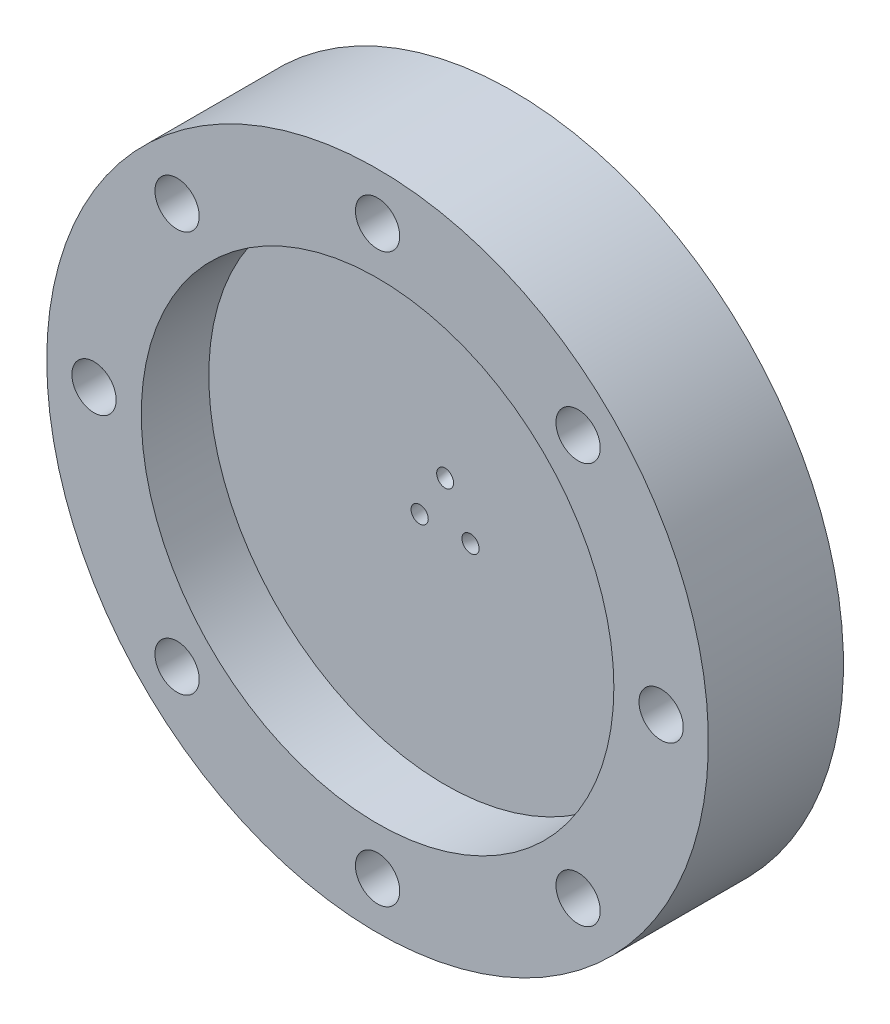
SolidWorks part; units mm, degrees
material "PLA (Polylactic Acid)"
ref_plane "Front Plane" through (0, 0, 0) normal (0, 0, 1) x (1, 0, 0)
ref_plane "Top Plane" through (0, 0, 0) normal (0, 1, 0) x (1, 0, 0)
ref_plane "Right Plane" through (0, 0, 0) normal (1, 0, 0) x (0, 0, -1)
sketch "Sketch2" plane through (0, 0, -1.7131) normal (0, 0, -1) x (-1, 0, 0)
  circle A0 centre (0, 0) radius 31.115
  dimension "D1" = 62.23
extrude "Boss-Extrude1" add sketch "Sketch2" along normal blind 12.7
sketch "Sketch3" plane through (0, 0, -14.4131) normal (0, 0, -1) x (-1, 0, 0)
  circle A0 centre (0, 26.67) radius 2.0828
  circle A1 centre (0, 0) radius 26.67 construction
  circle A2 centre (18.8585, 18.8585) radius 2.0828
  circle A4 centre (26.67, 0) radius 2.0828
  circle A5 centre (18.8585, -18.8585) radius 2.0828
  circle A6 centre (0, -26.67) radius 2.0828
  circle A7 centre (-18.8585, -18.8585) radius 2.0828
  circle A8 centre (-26.67, 0) radius 2.0828
  circle A9 centre (-18.8585, 18.8585) radius 2.0828
  point P23 (0, 0)
  dimension "D1" = 53.34
  dimension "D2" = 4.1656
  dimension "D3" = 8
extrude "Cut-Extrude3" cut sketch "Sketch3" against normal up to surface (12.7 mm away) up to face at (-31.115, 0, -1.7131)
sketch "Sketch4" plane through (0, 0, -1.7131) normal (0, 0, 1) x (1, 0, 0)
  circle A0 centre (0, 0) radius 22.225
  dimension "D1" = 44.45
extrude "Cut-Extrude2" cut sketch "Sketch4" against normal blind 6.35
sketch "Sketch6" plane through (0, 0, 0) normal (1, 0, 0) x (0, 0, -1)
  line L0 (-69.0368, 0) -> (69.0368, 0) construction
  line L1 (9.9681, 0) -> (9.9681, 6.35)
  line L2 (9.9681, 6.35) -> (12.5081, 6.35)
  line L3 (12.5081, 6.35) -> (12.5081, 2.0828)
  line L4 (12.5081, 2.0828) -> (14.4131, 2.0828)
  line L5 (14.4131, 2.0828) -> (14.4131, 0)
  line L6 (14.4131, 0) -> (9.9681, 0)
  line L7 (14.4131, -26.67) -> (14.4131, 26.67) construction
  line L8 (1.7131, 31.115) -> (1.7131, -31.115) construction
  point P3 (8.0631, 0)
  point P5 (0, 0)
  dimension "D1" = 6.35
  dimension "D2" = 1.905
  dimension "D3" = 6.35
  dimension "D4" = 1.905
revolve "Cut-Revolve2" cut sketch "Sketch6" angle 360 about L0
sketch "Sketch7" plane through (0, 0, 0) normal (1, 0, 0) x (0, 0, -1)
  line L0 (1.7131, 0) -> (-4.6369, 0) construction
  line L1 (1.7131, 31.115) -> (1.7131, -31.115) construction
  line L2 (9.9681, 6.35) -> (9.9681, -6.35) construction
  line L3 (9.9681, 3.175) -> (-4.6369, 0) construction
  dimension "D1" = 6.35
  dimension "D2" = 3.175
ref_plane "Plane1" through (0, 0, 4.6369) normal (0, -0.2124, 0.9772) x (1, 0, 0)
sketch "Sketch8" plane through (0, 0, 4.6369) normal (0, -0.2124, 0.9772) x (1, 0, 0)
  circle A0 centre (0, 0) radius 0.7937
  dimension "D1" = 1.5875
extrude "Cut-Extrude4" cut sketch "Sketch8" against normal up to surface (14.7736 mm away) up to face at (6.35, 0, -9.9681)
pattern_circular "CirPattern1" count 3 over 360 about axis through (0, 0, -1.7131) along (0, 0, 1) of "Cut-Extrude4"
